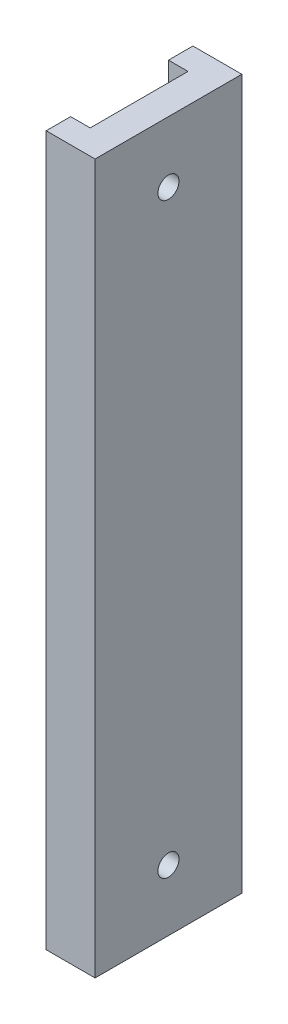
SolidWorks part; units mm, degrees
ref_plane "Front Plane" through (0, 0, 0) normal (0, 0, 1) x (1, 0, 0)
ref_plane "Top Plane" through (0, 0, 0) normal (0, 1, 0) x (1, 0, 0)
ref_plane "Right Plane" through (0, 0, 0) normal (1, 0, 0) x (0, 0, -1)
ref_plane "Plane1" through (0, 260, 0) normal (0, -1, 0) x (-1, 0, 0)
sketch "Sketch1" plane through (0, 260, 0) normal (0, -1, 0) x (-1, 0, 0)
  line L0 (71.5, -127.5) -> (61.5, -127.5)
  line L1 (61.5, -127.5) -> (61.5, -97.5)
  line L2 (61.5, -97.5) -> (71.5, -97.5)
  line L3 (71.5, -97.5) -> (71.5, -102.5)
  line L4 (71.5, -102.5) -> (67.5, -102.5)
  line L5 (67.5, -102.5) -> (67.5, -122.5)
  line L6 (67.5, -122.5) -> (71.5, -122.5)
  line L7 (71.5, -122.5) -> (71.5, -127.5)
  line L8 (68.9986, -122.5) -> (74.3631, -122.5) construction
  line L9 (68.9986, -102.5) -> (74.3631, -102.5) construction
  line L10 (67.5, -115.6369) -> (67.5, -121.0014) construction
  dimension "D1" = 5
  dimension "D2" = 10
  dimension "D3" = 6
extrude "Boss-Extrude1" add sketch "Sketch1" along normal blind 145
hole_wizard "M4 Clearance Hole1" positions "Sketch2" profile "Sketch4" hole size "M4" standard "ISO" end condition through all
sketch "Sketch2" plane through (-61.5, 0, 0) normal (1, 0, 0) x (0, 0, -1)
  line L0 (-112.5, 247.5) -> (-112.5, 127.5) construction
  line L2 (-97.5, 260) -> (-127.5, 260) construction
  line L4 (-112.5, 247.5) -> (-112.5, 260) construction
  line L7 (-112.5, 127.5) -> (-112.5, 115) construction
  line L8 (-97.5, 115) -> (-127.5, 115) construction
  point P1 (-112.5, 247.5)
  point P2 (-112.5, 127.5)
  point P7 (-112.5, 260)
  point P23 (-112.5, 125.4797)
  dimension "D1" = 120
sketch "Sketch4" plane through (-61.5, 247.5, 112.5) normal (0, 1, 0) x (0, 0, -1)
  line L0 (0, 0) -> (0, 10)
  line L1 (0, 10) -> (2.15, 10)
  line L2 (2.15, 10) -> (2.15, 0)
  line L5 (2.15, 0) -> (0, 0)
  line L11 (0, -6.35) -> (0, 107.95) construction
  dimension "Thru Hole Dia." = 4.3
  dimension "Thru Hole Depth" = 10
